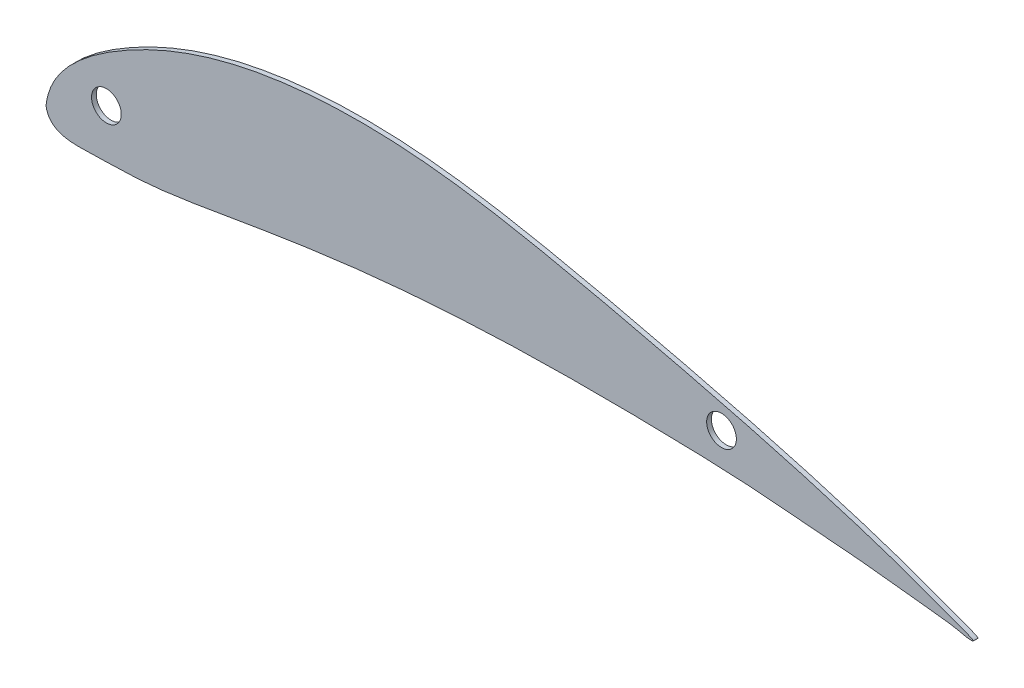
SolidWorks part; units mm, degrees
material "Balsa"
ref_plane "Front Plane" through (0, 0, 0) normal (0, 0, 1) x (1, 0, 0)
ref_plane "Top Plane" through (0, 0, 0) normal (0, 1, 0) x (1, 0, 0)
ref_plane "Right Plane" through (0, 0, 0) normal (1, 0, 0) x (0, 0, -1)
sketch "Sketch1" plane through (0, 0, 0) normal (0, 0, 1) x (1, 0, 0)
  spline S0 degree 3 poles (0.0006, 0.0001) (0.8106, 7.3592) (8.6491, 17.8566) (26.2867, 29.9752) (52.1111, 42.0692) (89.5976, 49.2908) (131.4008, 47.8848) (173.2567, 40.0411) (217.9611, 29.613) (256.9521, 19.5289) (290.3598, 8.711) (301.2732, 4.3828) (314.8169, -0.5162) (309.8463, 0.0001) knots 0 0 0 0 0.060864 0.113688 0.188609 0.312909 0.448482 0.557612 0.691544 0.852438 0.929756 0.976058 1 1 1 1
  spline S1 degree 3 poles (309.8463, 0.0001) (303.9568, 1.471) (293.9895, 2.094) (276.264, 4.5144) (260.8463, 5.4274) (235.8588, 7.8703) (205.1014, 8.8381) (157.7186, 9.0307) (110.4973, 6.1815) (66.5062, -0.5867) (36.4547, -6.0985) (15.3166, -6.1891) (1.2307, -6.9241) (0.0006, 0.0001) knots 0 0 0 0 0.057787 0.095275 0.171021 0.205339 0.335319 0.464904 0.658702 0.785512 0.893517 0.943092 1 1 1 1
extrude "Boss-Extrude1" add sketch "Sketch1" along normal blind 1.5875
sketch "Sketch2" plane through (0, 0, 1.5875) normal (0, 0, 1) x (1, 0, 0)
  line L0 (227.2963, 19.0501) -> (20.32, 10.16) construction
  line L1 (20.32, 10.16) -> (227.2963, 10.16) construction
  line L2 (227.2963, 10.16) -> (227.2963, 19.0501) construction
  circle A0 centre (20.32, 10.16) radius 5
  circle A1 centre (227.2963, 19.0501) radius 5
  dimension "D2" = 10
  dimension "D3" = 10
  dimension "D6" = 20.32
  dimension "D1" = 82.55
  dimension "D4" = 19.05
  dimension "D5" = 10.16
extrude "Cut-Extrude1" cut sketch "Sketch2" against normal through all
sketch "Sketch3" plane through (0, 0, 0) normal (0, 0, -1) x (-1, 0, 0)
  line L0 (-309.8463, 0.0001) -> (-259.6129, 0.0001)
